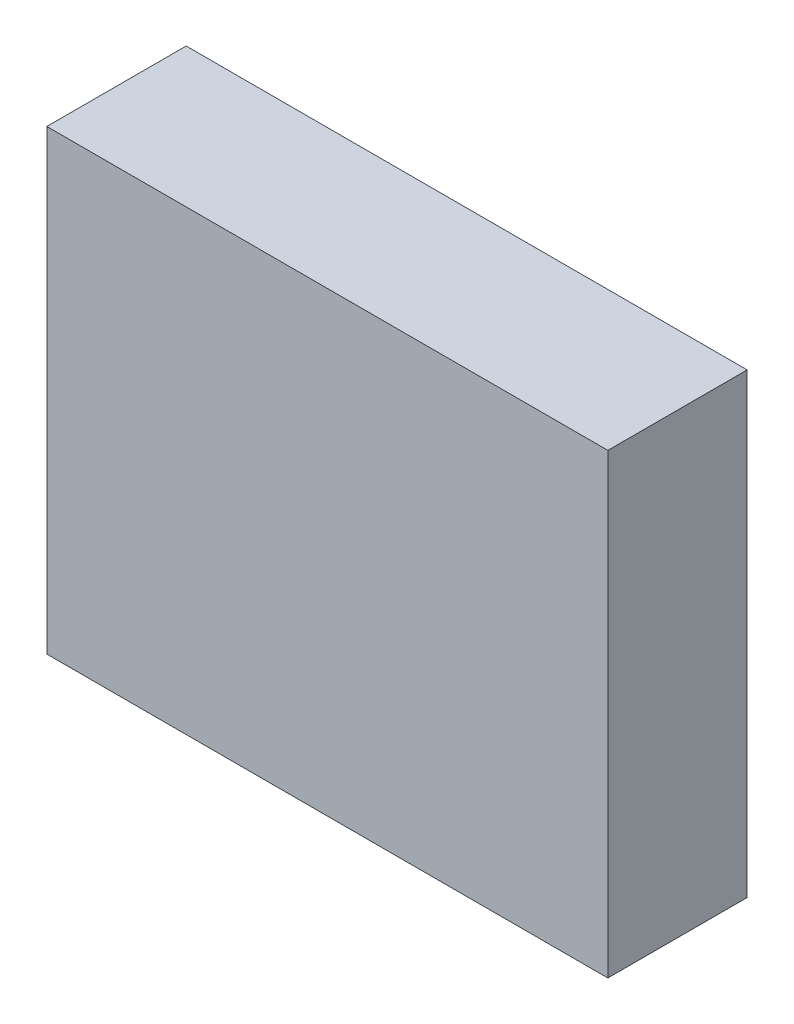
SolidWorks part; units mm, degrees
material "POM Acetal Copolymer"
ref_plane "Front Plane" through (0, 0, 0) normal (0, 0, 1) x (1, 0, 0)
ref_plane "Top Plane" through (0, 0, 0) normal (0, 1, 0) x (1, 0, 0)
ref_plane "Right Plane" through (0, 0, 0) normal (1, 0, 0) x (0, 0, -1)
sketch "Sketch1" plane through (0, 0, 0) normal (0, 0, 1) x (1, 0, 0)
  line L1 (31, -25.25) -> (-31, -25.25)
  line L2 (31, -25.25) -> (31, 25.25)
  line L3 (31, 25.25) -> (-31, 25.25)
  line L4 (-31, -25.25) -> (-31, 25.25)
  line L5 (31, -25.25) -> (-31, 25.25) construction
  line L6 (31, 25.25) -> (-31, -25.25) construction
  point P0 (0, 0)
  dimension "D1" = 50.5
  dimension "D2" = 62
extrude "Boss-Extrude1" add sketch "Sketch1" along normal blind 15.4
